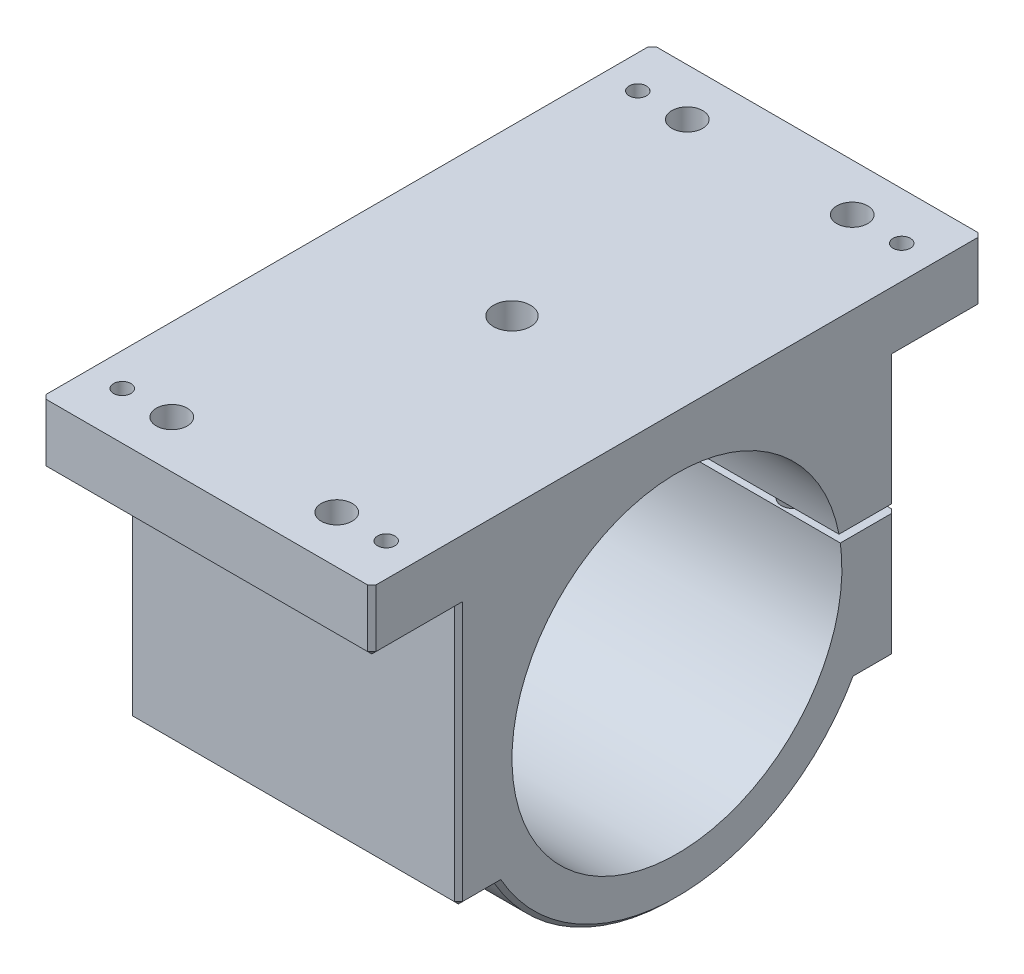
SolidWorks part; units mm, degrees
ref_plane "Front Plane" through (0, 0, 0) normal (0, 0, 1) x (1, 0, 0)
ref_plane "Top Plane" through (0, 0, 0) normal (0, 1, 0) x (1, 0, 0)
ref_plane "Right Plane" through (0, 0, 0) normal (1, 0, 0) x (0, 0, -1)
sketch "Sketch1" plane through (0, 0, 0) normal (1, 0, 0) x (0, 0, -1)
  line L0 (0, 122.2832) -> (0, 20.7221) construction
  line L1 (-53, -25) -> (-43.3013, -25)
  line L2 (-53, -25) -> (-53, 38)
  line L3 (-53, 38) -> (-74, 38)
  line L4 (-74, 38) -> (-74, 53)
  line L5 (-74, 53) -> (74, 53)
  line L6 (53, -25) -> (43.3013, -25)
  line L7 (74, 38) -> (74, 53)
  line L8 (53, 38) -> (74, 38)
  line L9 (53, -25) -> (53, 38)
  arc A0 (-43.3013, -25) -> (43.3013, -25) centre (0, 0) ccw
  circle A1 centre (0, 0) radius 40
  point P13 (0, 53)
  dimension "D5" = 80
  dimension "D6" = 50
  dimension "D1" = 148
  dimension "D2" = 15
  dimension "D3" = 21
  dimension "D4" = 63
  dimension "D7" = 53
extrude "Boss-Extrude1" add sketch "Sketch1" along normal mid plane 80
sketch "Sketch2" plane through (0, 0, -53) normal (0, 0, -1) x (-1, 0, 0)
  line L0 (-40, -25) -> (-40, 38) construction
  line L1 (-40, 7.5) -> (40, 7.5)
  line L2 (-40, 7.5) -> (-40, 5.5)
  line L3 (-40, 5.5) -> (40, 5.5)
  line L4 (40, 7.5) -> (40, 5.5)
  line L5 (40, -25) -> (40, 38) construction
  line L6 (-40, 38) -> (40, 38) construction
  dimension "D1" = 2
  dimension "D2" = 30.5
extrude "Cut-Extrude1" cut sketch "Sketch2" against normal blind 19
sketch "Sketch3" plane through (0, -25, 0) normal (0, -1, 0) x (1, 0, 0)
  line L0 (25, -43.3) -> (25, -53) construction
  line L1 (40, -53) -> (-40, -53) construction
  line L2 (25, -43.3) -> (40, -43.3013) construction
  circle A0 centre (25, -43.3) radius 5.5
  dimension "D1" = 11
  dimension "D2" = 9.7
  dimension "D3" = 15
extrude "Cut-Extrude2" cut sketch "Sketch3" along normal through all from offset 3 offset against normal yes
sketch "Sketch4" plane through (0, -22, 0) normal (0, -1, 0) x (1, 0, 0)
  circle A0 centre (25, -43.3) radius 3
  dimension "D1" = 6
extrude "Cut-Extrude3" cut sketch "Sketch4" against normal blind 64.5
pattern_linear "LPattern1" count 3 spacing 25 along (-1, 0, 0) of "Cut-Extrude3", "Cut-Extrude2"
sketch "Sketch5" plane through (0, 53, 0) normal (0, 1, 0) x (1, 0, 0)
  line L0 (-32, 62.5) -> (-20, 62.5) construction
  line L1 (40, 74) -> (-40, 74) construction
  line L2 (-40, 74) -> (-40, -74) construction
  line L3 (-72.0395, 0) -> (41.5363, 0) construction
  line L4 (0, 89.2861) -> (0, -18.3375) construction
  circle A0 centre (0, 0) radius 4.5
  circle A1 centre (-32, 62.5) radius 2.1
  circle A2 centre (-20, 62.5) radius 3.75
  circle A3 centre (32, 62.5) radius 2.1
  circle A4 centre (20, 62.5) radius 3.75
  circle A5 centre (32, -62.5) radius 2.1
  circle A6 centre (20, -62.5) radius 3.75
  circle A7 centre (-20, -62.5) radius 3.75
  circle A8 centre (-32, -62.5) radius 2.1
  dimension "D1" = 7.5
  dimension "D2" = 4.2
  dimension "D6" = 9
  dimension "D3" = 12
  dimension "D4" = 11.5
  dimension "D5" = 8
extrude "Cut-Extrude4" cut sketch "Sketch5" against normal blind 24.5
chamfer "Chamfer1" distance 1 angle 45 24 edges at (40, 22.75, -53) (40, 38, -63.5) (40, 45.5, -74) (0, 38, -74) (-40, 45.5, -74) (-40, 38, -63.5) (-40, 22.75, -53) (40, 6.5, 53) (-40, 6.5, 53) (0, 38, 74) (40, 45.5, 74) (40, 38, 63.5) (-40, 38, 63.5) (-40, 45.5, 74) (40, -9.75, -53) (-40, -9.75, -53) (40, -25, -48.1506) (0, -25, -53) (-40, -25, -48.1506) (40, -50, 0) (40, -25, 48.1506) (0, -25, 53) (-40, -25, 48.1506) (-40, -50, 0)
